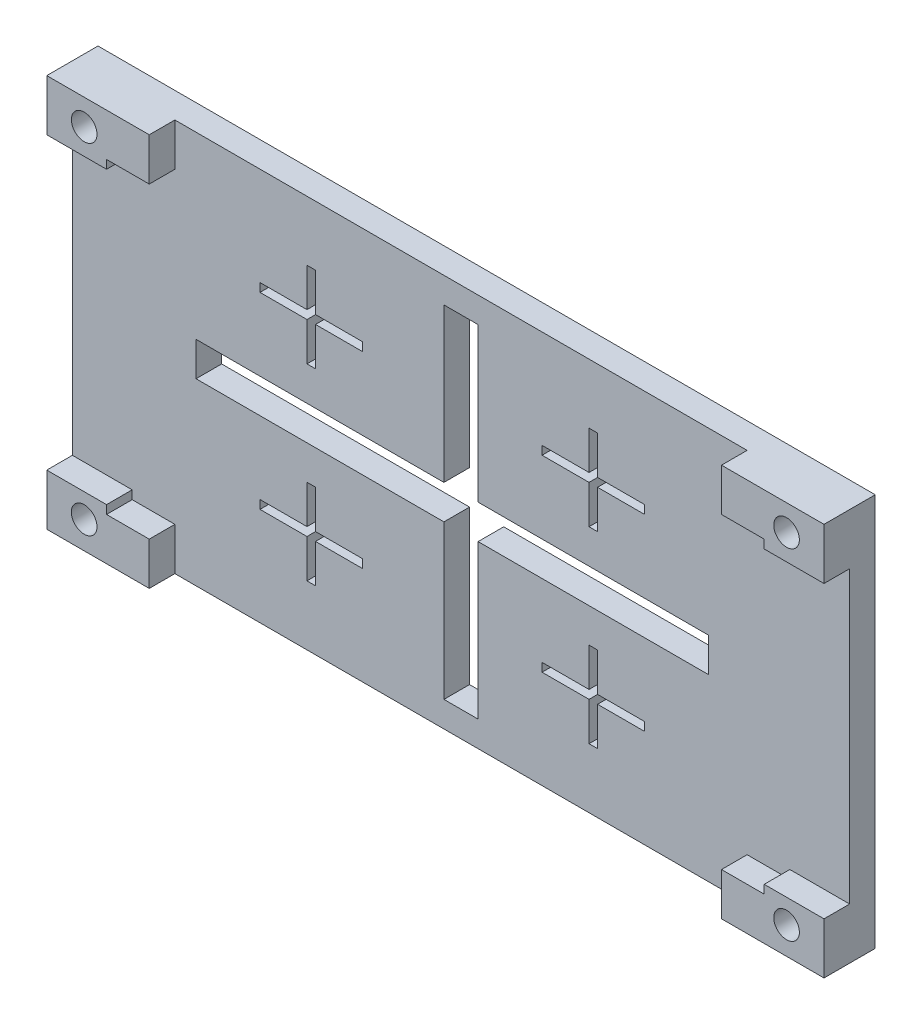
SolidWorks part; units mm, degrees
ref_plane "Front Plane" through (0, 0, 0) normal (0, 0, 1) x (1, 0, 0)
ref_plane "Top Plane" through (0, 0, 0) normal (0, 1, 0) x (1, 0, 0)
ref_plane "Right Plane" through (0, 0, 0) normal (1, 0, 0) x (0, 0, -1)
sketch "Sketch1" plane through (0, 0, 0) normal (0, 0, 1) x (1, 0, 0)
  line L0 (37.4777, 40.9123) -> (37.4777, -5.0877) construction
  line L5 (-7, 17.9123) -> (84, 17.9123) construction
  line L7 (-7, 30.9123) -> (-7, 40.9123)
  line L8 (40.5, 19.9123) -> (67.4777, 19.9123)
  line L9 (36.5, 37.9123) -> (40.5, 37.9123)
  line L10 (-7, 40.9123) -> (5, 40.9123)
  line L11 (36.5, 37.9123) -> (36.5, 19.9123)
  line L13 (36.5, -2.0877) -> (40.5, -2.0877)
  line L14 (-7, -5.0877) -> (5, -5.0877)
  line L15 (-7, 4.9123) -> (-7, -5.0877)
  line L16 (40.5, 37.9123) -> (40.5, 19.9123)
  line L17 (7.4777, 15.9123) -> (36.5, 15.9123)
  line L18 (84, -5.0877) -> (69.9555, -5.0877)
  line L19 (84, 4.9123) -> (84, -5.0877)
  line L20 (7.4777, 15.9123) -> (7.4777, 19.9123)
  line L21 (7.4777, 19.9123) -> (36.5, 19.9123)
  line L22 (84, 30.9123) -> (84, 40.9123)
  line L23 (67.4777, 15.9123) -> (67.4777, 19.9123)
  line L24 (84, 40.9123) -> (69.9555, 40.9123)
  line L30 (7.4777, 15.9123) -> (67.4777, 19.9123) construction
  line L31 (7.4777, 19.9123) -> (67.4777, 15.9123) construction
  line L35 (40.5, 18.1138) -> (40.5, 17.7108)
  line L37 (5, 40.9123) -> (69.9555, 40.9123)
  line L38 (84, 30.9123) -> (84, 4.9123)
  line L40 (5, -5.0877) -> (69.9555, -5.0877)
  line L41 (-7, 30.9123) -> (-7, 4.9123)
  line L42 (40.5, 15.9123) -> (40.5, -2.0877)
  line L43 (40.5, 15.9123) -> (67.4777, 15.9123)
  line L44 (36.5, 15.9123) -> (36.5, -2.0877)
  line L45 (36.5, 17.9775) -> (36.5, 17.8471)
  line L46 (40.5, 37.9123) -> (67.4777, 19.9123) construction
  line L49 (53.4889, 23.9123) -> (54.4889, 23.9123)
  line L50 (53.4889, 23.9123) -> (53.4889, 28.4123)
  line L51 (53.4889, 33.9123) -> (54.4889, 33.9123)
  line L52 (54.4889, 23.9123) -> (54.4889, 28.4123)
  line L53 (53.4889, 23.9123) -> (54.4889, 33.9123) construction
  line L54 (53.4889, 33.9123) -> (54.4889, 23.9123) construction
  line L56 (59.9889, 28.4123) -> (54.4889, 28.4123)
  line L57 (59.9889, 28.4123) -> (59.9889, 29.4123)
  line L58 (59.9889, 29.4123) -> (54.4889, 29.4123)
  line L59 (47.9889, 28.4123) -> (47.9889, 29.4123)
  line L60 (59.9889, 28.4123) -> (47.9889, 29.4123) construction
  line L61 (59.9889, 29.4123) -> (47.9889, 28.4123) construction
  line L63 (54.4889, 29.4123) -> (54.4889, 33.9123)
  line L65 (53.4889, 28.4123) -> (47.9889, 28.4123)
  line L66 (53.4889, 29.4123) -> (47.9889, 29.4123)
  line L67 (53.4889, 29.4123) -> (53.4889, 33.9123)
  line L68 (21.4666, 23.9123) -> (21.4666, 28.4123)
  line L69 (21.4666, 28.4123) -> (26.9666, 28.4123)
  line L70 (26.9666, 28.4123) -> (26.9666, 29.4123)
  line L71 (21.4666, 29.4123) -> (26.9666, 29.4123)
  line L72 (21.4666, 29.4123) -> (21.4666, 33.9123)
  line L73 (21.4666, 33.9123) -> (20.4666, 33.9123)
  line L74 (20.4666, 29.4123) -> (20.4666, 33.9123)
  line L75 (14.9666, 29.4123) -> (20.4666, 29.4123)
  line L76 (14.9666, 28.4123) -> (14.9666, 29.4123)
  line L77 (14.9666, 28.4123) -> (20.4666, 28.4123)
  line L78 (20.4666, 23.9123) -> (20.4666, 28.4123)
  line L79 (21.4666, 23.9123) -> (20.4666, 23.9123)
  line L80 (53.4889, 11.9123) -> (53.4889, 7.4123)
  line L81 (53.4889, 7.4123) -> (47.9889, 7.4123)
  line L82 (47.9889, 7.4123) -> (47.9889, 6.4123)
  line L83 (53.4889, 6.4123) -> (47.9889, 6.4123)
  line L84 (53.4889, 6.4123) -> (53.4889, 1.9123)
  line L85 (53.4889, 1.9123) -> (54.4889, 1.9123)
  line L86 (54.4889, 6.4123) -> (54.4889, 1.9123)
  line L87 (59.9889, 6.4123) -> (54.4889, 6.4123)
  line L88 (59.9889, 7.4123) -> (59.9889, 6.4123)
  line L89 (59.9889, 7.4123) -> (54.4889, 7.4123)
  line L90 (54.4889, 11.9123) -> (54.4889, 7.4123)
  line L91 (53.4889, 11.9123) -> (54.4889, 11.9123)
  line L92 (21.4666, 11.9123) -> (20.4666, 11.9123)
  line L93 (20.4666, 11.9123) -> (20.4666, 7.4123)
  line L94 (14.9666, 7.4123) -> (20.4666, 7.4123)
  line L95 (14.9666, 7.4123) -> (14.9666, 6.4123)
  line L96 (14.9666, 6.4123) -> (20.4666, 6.4123)
  line L97 (20.4666, 6.4123) -> (20.4666, 1.9123)
  line L98 (21.4666, 1.9123) -> (20.4666, 1.9123)
  line L99 (21.4666, 6.4123) -> (21.4666, 1.9123)
  line L100 (21.4666, 6.4123) -> (26.9666, 6.4123)
  line L101 (26.9666, 7.4123) -> (26.9666, 6.4123)
  line L102 (21.4666, 7.4123) -> (26.9666, 7.4123)
  line L103 (21.4666, 11.9123) -> (21.4666, 7.4123)
  line L104 (38.5, -9.3456) -> (38.5, 40.9123) construction
  line L105 (-7, -5.0877) -> (84, -5.0877) construction
  line L106 (-7, -5.0877) -> (-7, -9.3456) construction
  line L107 (-7, -9.3456) -> (84, -9.3456) construction
  line L108 (84, -5.0877) -> (84, -9.3456) construction
  point P5 (0, 17.9123)
  point P10 (37.4777, 17.9123)
  point P13 (0, 30.9123)
  point P38 (53.9889, 28.9123)
  point P43 (53.9889, 28.9123)
  point P51 (53.9889, 23.9123)
  point P98 (38.5, 37.9123)
  dimension "D14" = 40
  dimension "D16" = 20
  dimension "D17" = 23
  dimension "D13" = 4
  dimension "D19" = 4
  dimension "D20" = 30
  dimension "D21" = 1
  dimension "D22" = 1
  dimension "D23" = 5
  dimension "D24" = 6
  dimension "D25" = 6
  dimension "D26" = 5.5
extrude "Boss-Extrude1" add sketch "Sketch1" along normal blind 3 contours L7 L41 L15 L14 L40 L18 L19 L38 L22 L24 L37 L10 L44 L17 L20 L21 L11 L9 L16 L8 L23 L43 L42 L13 L66 L67 L51 L63 L58 L57 L56 L52 L49 L50 L65 L59 L68 L79 L78 L77 L76 L75 L74 L73 region at (-5.9803, 35.9123, 0)
sketch "Sketch3" plane through (0, 0, 3) normal (0, 0, 1) x (1, 0, 0)
  line L0 (38.5, 40.9123) -> (38.5, -5.0877) construction
  line L1 (84, 40.9123) -> (-7, 40.9123) construction
  line L2 (-7, -5.0877) -> (84, -5.0877) construction
  line L3 (-7, 17.9123) -> (84, 17.9123) construction
  line L4 (-7, -5.0877) -> (-7, 40.9123) construction
  line L5 (84, 40.9123) -> (84, -5.0877) construction
  line L6 (-7, -5.0877) -> (-7, 0.9123)
  line L7 (-7, -5.0877) -> (5, -5.0877)
  line L8 (-7, 0.9123) -> (0, 0.9123)
  line L9 (0, 0.9123) -> (0, -0.0877)
  line L10 (0, -0.0877) -> (5, -0.0877)
  line L11 (5, -0.0877) -> (5, -5.0877)
  line L12 (0, 35.9123) -> (5, 35.9123)
  line L13 (0, 34.9123) -> (0, 35.9123)
  line L14 (-7, 34.9123) -> (0, 34.9123)
  line L15 (-7, 40.9123) -> (-7, 34.9123)
  line L16 (-7, 40.9123) -> (5, 40.9123)
  line L17 (5, 35.9123) -> (5, 40.9123)
  line L18 (77, -0.0877) -> (72, -0.0877)
  line L19 (77, 0.9123) -> (77, -0.0877)
  line L20 (84, 0.9123) -> (77, 0.9123)
  line L21 (84, -5.0877) -> (84, 0.9123)
  line L22 (84, -5.0877) -> (72, -5.0877)
  line L23 (72, -0.0877) -> (72, -5.0877)
  line L24 (77, 34.9123) -> (77, 35.9123)
  line L25 (84, 34.9123) -> (77, 34.9123)
  line L26 (84, 40.9123) -> (84, 34.9123)
  line L27 (84, 40.9123) -> (72, 40.9123)
  line L28 (72, 35.9123) -> (72, 40.9123)
  line L29 (77, 35.9123) -> (72, 35.9123)
  dimension "D1" = 6
  dimension "D2" = 12
  dimension "D3" = 7
  dimension "D4" = 1
  dimension "D5" = 5
extrude "Boss-Extrude2" add sketch "Sketch3" along normal blind 3
sketch "Sketch5" plane through (0, 0, 0) normal (0, 0, 1) x (1, 0, 0)
  line L0 (38.5, 36) -> (38.5, 0) construction
  line L1 (0, 0) -> (77, 0)
  line L2 (0, 0) -> (0, 36)
  line L3 (0, 36) -> (77, 36)
  line L4 (77, 0) -> (77, 36)
  line L5 (0, 18) -> (77, 18) construction
  line L6 (-4.1765, 0.9) -> (-1.0588, 0.9)
  line L7 (-7, 31) -> (-7, 41)
  line L8 (-7, 31) -> (0, 31)
  line L9 (0, 31) -> (0, 36)
  line L10 (-7, 41) -> (5, 41)
  line L11 (5, 41) -> (5, 36)
  line L12 (0, 31) -> (0, 36)
  line L13 (5, -5) -> (5, 0)
  line L14 (-7, -5) -> (5, -5)
  line L15 (-7, 5) -> (-7, -5)
  line L16 (-7, 5) -> (0, 5)
  line L17 (72, -5) -> (72, 0)
  line L18 (84, -5) -> (72, -5)
  line L19 (84, 5) -> (84, -5)
  line L20 (84, 5) -> (77, 5)
  line L21 (84, 31) -> (77, 31)
  line L22 (84, 31) -> (84, 41)
  line L23 (72, 41) -> (72, 36)
  line L24 (84, 41) -> (72, 41)
  line L29 (0, 5) -> (0, 0)
  line L30 (72, 0) -> (77, 0)
  line L31 (72, 36) -> (77, 36)
  line L35 (5, 36) -> (72, 36)
  line L36 (0, 31) -> (0, 36)
  line L37 (5, 41) -> (72, 41)
  line L38 (84, 31) -> (84, 5)
  line L39 (0, 5) -> (0, 0)
  line L40 (5, -5) -> (72, -5)
  line L41 (-7, 31) -> (-7, 5)
  line L66 (-5.7354, -1.8) -> (-4.1765, 0.9)
  line L73 (-1.0588, 35.1) -> (0.5, 37.8)
  line L74 (0.5, 37.8) -> (-1.0588, 40.5)
  line L75 (-1.0588, 40.5) -> (-4.1765, 40.5)
  line L76 (-4.1765, 40.5) -> (-5.7354, 37.8)
  line L77 (-5.7354, 37.8) -> (-4.1765, 35.1)
  line L78 (-4.1765, 35.1) -> (-1.0588, 35.1)
  line L79 (-4.1765, -4.5) -> (-5.7354, -1.8)
  line L80 (-1.0588, -4.5) -> (-4.1765, -4.5)
  line L81 (0.5, -1.8) -> (-1.0588, -4.5)
  line L82 (-1.0588, 0.9) -> (0.5, -1.8)
  line L83 (82.7354, -1.8) -> (81.1765, 0.9)
  line L84 (81.1765, -4.5) -> (82.7354, -1.8)
  line L85 (78.0588, -4.5) -> (81.1765, -4.5)
  line L86 (76.5, -1.8) -> (78.0588, -4.5)
  line L87 (78.0588, 0.9) -> (76.5, -1.8)
  line L88 (81.1765, 0.9) -> (78.0588, 0.9)
  line L89 (81.1765, 35.1) -> (78.0588, 35.1)
  line L90 (82.7354, 37.8) -> (81.1765, 35.1)
  line L91 (81.1765, 40.5) -> (82.7354, 37.8)
  line L92 (78.0588, 40.5) -> (81.1765, 40.5)
  line L93 (76.5, 37.8) -> (78.0588, 40.5)
  line L94 (78.0588, 35.1) -> (76.5, 37.8)
  line L96 (29, 8.5) -> (48, 8.5) construction
  line L97 (29, 8.5) -> (29, 27.5) construction
  line L98 (29, 27.5) -> (48, 27.5) construction
  line L99 (48, 8.5) -> (48, 27.5) construction
  line L100 (29, 8.5) -> (48, 27.5) construction
  line L101 (29, 27.5) -> (48, 8.5) construction
  circle A0 centre (-2.6177, 37.8) radius 2.5 construction
  circle A5 centre (-2.6177, 37.9) radius 1.5
  circle A6 centre (-2.6177, -1.9) radius 1.5
  circle A7 centre (79.6177, -1.9) radius 1.5
  circle A8 centre (79.6177, 37.9) radius 1.5
  circle A9 centre (29, 8.5) radius 1.5
  circle A10 centre (29, 27.5) radius 1.5
  circle A11 centre (48, 27.5) radius 1.5
  circle A12 centre (48, 8.5) radius 1.5
  point P5 (0, 18)
  point P13 (0, 31)
  point P64 (38.5, 18)
  dimension "D12" = 19
  dimension "D10" = 5
  dimension "D11" = 3
  dimension "D14" = 3
  dimension "D15" = 3
  dimension "D16" = 3
  dimension "D17" = 3
  dimension "D1" = 77
  dimension "D2" = 36
  dimension "D3" = 5
  dimension "D4" = 5
  dimension "D5" = 7
  dimension "D6" = 5
  dimension "D7" = 5.4
  dimension "D8" = 0.5
  dimension "D9" = 0.5
  dimension "D13" = 19
  dimension "D18" = 29
  dimension "D19" = 79.6177
  dimension "D20" = 0.9
  dimension "D21" = 37.9
extrude "Cut-Extrude7" cut sketch "Sketch5" along normal through all contours A7
extrude "Cut-Extrude8" cut sketch "Sketch5<26>" along normal through all contours A6 | A5 | A8
sketch "Sketch5<26>" plane through (0, 0, 0) normal (0, 0, 1) x (1, 0, 0) same geometry as "Sketch5"
